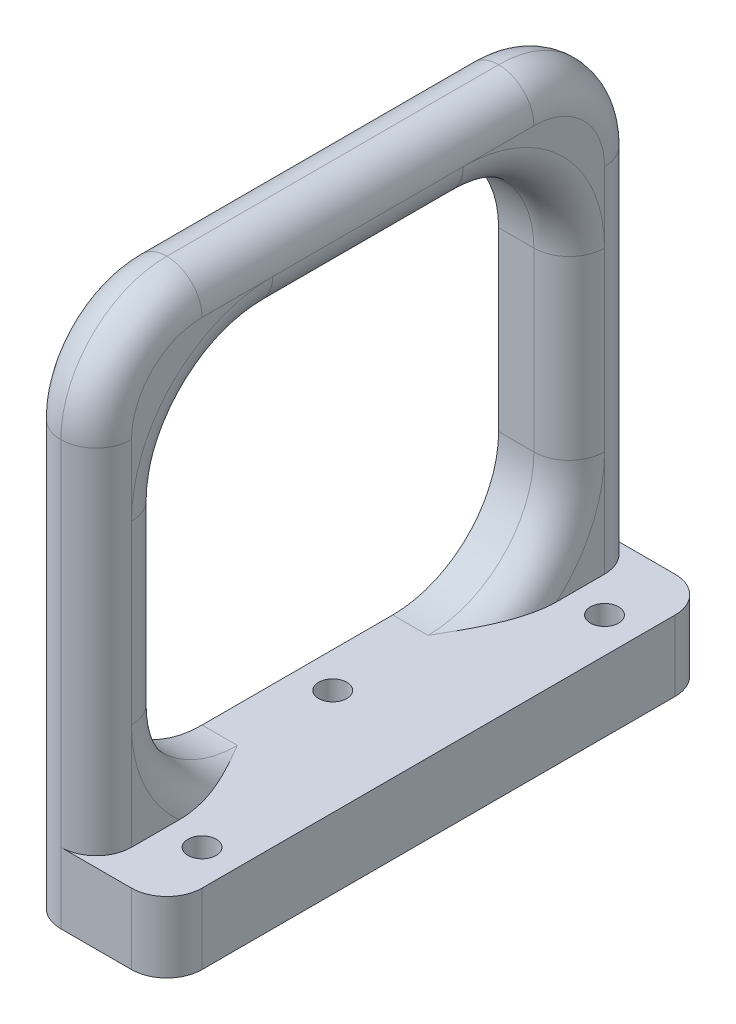
SolidWorks part; units mm, degrees
ref_plane "前视基准面" through (0, 0, 0) normal (0, 0, 1) x (1, 0, 0)
ref_plane "上视基准面" through (0, 0, 0) normal (0, 1, 0) x (1, 0, 0)
ref_plane "右视基准面" through (0, 0, 0) normal (1, 0, 0) x (0, 0, -1)
other "Configuration Table"
sketch "草图1" plane through (0, 0, 0) normal (1, 0, 0) x (0, 0, -1)
  line L1 (30.8, -30) -> (-30.8, -30)
  line L2 (30.8, -30) -> (30.8, 30)
  line L3 (30.8, 30) -> (-30.8, 30)
  line L4 (-30.8, -30) -> (-30.8, 30)
  line L5 (30.8, -30) -> (-30.8, 30) construction
  line L6 (30.8, 30) -> (-30.8, -30) construction
  line L7 (22.8, -30) -> (-22.8, -30)
  line L8 (22.8, -30) -> (22.8, 22)
  line L9 (22.8, 22) -> (-22.8, 22)
  line L10 (-22.8, -30) -> (-22.8, 22)
  line L11 (22.8, -30) -> (-22.8, 22) construction
  line L12 (22.8, 22) -> (-22.8, -30) construction
  point P0 (0, 0)
  point P6 (0, -4)
  point P11 (0, 30)
  dimension "D1" = 60
  dimension "D2" = 61.6
  dimension "D3" = 8
  dimension "D4" = 8
  dimension "D5" = 8
extrude "凸台-拉伸1" add sketch "草图1" along normal blind 8 contours L1 L10 L9 L8 L2 L3 L4 region at (0, -29.1401, -26.8)
sketch "草图2" plane through (0, -30, 0) normal (0, -1, 0) x (1, 0, 0)
  line L0 (8, -30.8) -> (0, -30.8) construction
  line L1 (0, 30.8) -> (16, 30.8)
  line L2 (0, 30.8) -> (0, -30.8)
  line L3 (0, -30.8) -> (16, -30.8)
  line L4 (16, 30.8) -> (16, -30.8)
  dimension "D1" = 16
extrude "凸台-拉伸2" add sketch "草图2" against normal blind 8
sketch "草图3" plane through (0, -22, 0) normal (0, 1, 0) x (1, 0, 0)
  line L1 (0, 0) -> (16, 0) construction
  line L2 (16, 30.8) -> (16, -30.8) construction
  line L3 (8, 22.8) -> (8, 30.8) construction
  line L4 (12, 22.8) -> (12, -22.4171) construction
  line L5 (8, 30.8) -> (16, 30.8) construction
  circle A0 centre (4, 0) radius 1.6
  circle A1 centre (12, 22.8) radius 1.6
  circle A2 centre (12, -22.8) radius 1.6
  point P16 (4, 0)
  dimension "D1" = 3.2
  dimension "D3" = 3.2
  dimension "D2" = 8
  dimension "D4" = 4
  dimension "D5" = 8
extrude "切除-拉伸1" cut sketch "草图3" against normal up to next contours A0 | A1 | A2
fillet "圆角1" radius 12 6 edges at (4, 30, -30.8) (4, 30, 30.8) (4, -22, -22.8) (4, 22, -22.8) (4, -22, 22.8) (4, 22, 22.8)
fillet "圆角2" radius 4 19 edges at (8, -18.4853, 19.2853) (8, -18.4853, -19.2853) (8, 0, -22.8) (8, 18.4853, -19.2853) (8, 22, 0) (8, 18.4853, 19.2853) (8, -2, -30.8) (8, 26.4853, -27.2853) (8, 30, 0) (8, 26.4853, 27.2853) (0, -6, -30.8) (0, 26.4853, -27.2853) (0, 30, 0) (0, 26.4853, 27.2853) (8, 0, 22.8) (8, -2, 30.8) (0, -6, 30.8) (16, -26, -30.8) (16, -26, 30.8)
